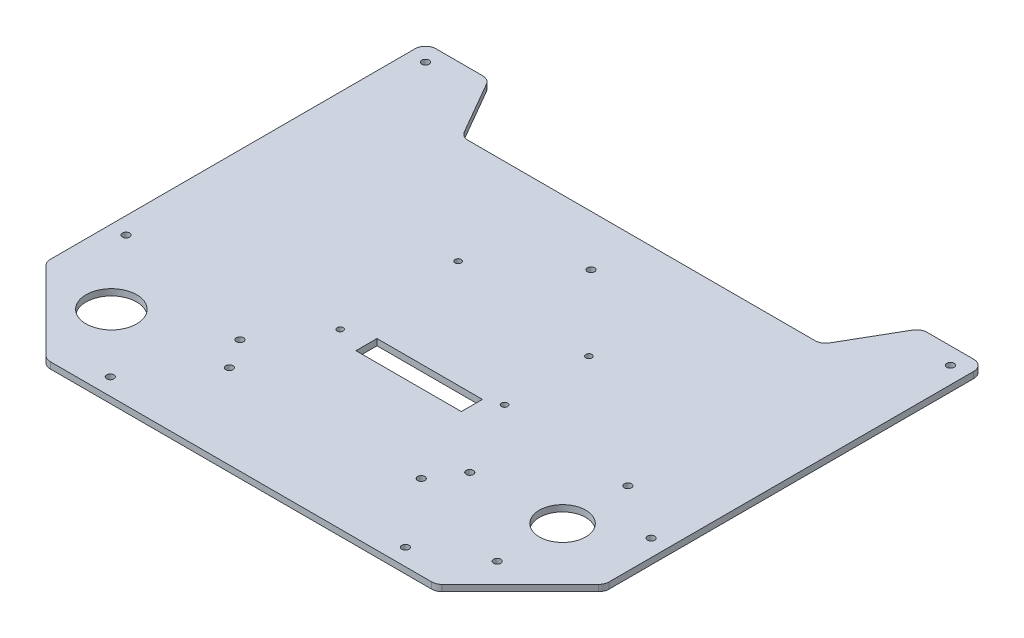
SolidWorks part; units mm, degrees
material "Acier non allié"
ref_plane "Front" through (0, 0, 0) normal (0, 0, 1) x (1, 0, 0)
ref_plane "Top" through (0, 0, 0) normal (0, 1, 0) x (1, 0, 0)
ref_plane "Right" through (0, 0, 0) normal (1, 0, 0) x (0, 0, -1)
sketch "Esquisse1" plane through (0, 0, 0) normal (0, 1, 0) x (1, 0, 0)
  line L0 (0, 0) -> (0, 1919.0564) construction
  line L1 (-92.5, 0) -> (92.5, 0)
  line L2 (92.5, 0) -> (132.5, 40)
  line L3 (132.5, 40) -> (132.5, 220)
  line L4 (132.5, 220) -> (102.5, 220)
  line L5 (102.5, 220) -> (85.1795, 190)
  line L6 (85.1795, 190) -> (-85.1795, 190)
  line L7 (-102.5, 220) -> (-85.1795, 190)
  line L8 (-132.5, 220) -> (-102.5, 220)
  line L9 (-132.5, 40) -> (-132.5, 220)
  line L10 (-92.5, 0) -> (-132.5, 40)
  point P12 (0, 190)
  dimension "D1" = 132.5
  dimension "D2" = 220
  dimension "D3" = 30
  dimension "D4" = 30
  dimension "D5" = 40
  dimension "D6" = 40
  dimension "D7" = 60
extrude "Boss.-Extru.1" add sketch "Esquisse1" along normal blind 3
fillet "Congé1" radius 5 10 edges at (132.5, 1.5, -220) (102.5, 1.5, -220) (85.1795, 1.5, -190) (-85.1795, 1.5, -190) (-102.5, 1.5, -220) (-132.5, 1.5, -220) (-132.5, 1.5, -40) (-92.5, 1.5, 0) (92.5, 1.5, 0) (132.5, 1.5, -40)
sketch "Esquisse2" plane through (0, 0, 0) normal (0, -1, 0) x (1, 0, 0)
  line L0 (0, 0) -> (0, -330.9968) construction
  line L1 (-90.4289, 0) -> (90.4289, 0) construction
  line L2 (-105.3868, -220) -> (-127.5, -220) construction
  line L3 (-132.5, -215) -> (-132.5, -42.0711) construction
  circle A0 centre (-70, -8) radius 1
  circle A1 centre (-124.5, -70) radius 1
  circle A2 centre (-124.5, -212) radius 1
  circle A3 centre (124.5, -212) radius 1
  circle A4 centre (124.5, -70) radius 1
  circle A5 centre (70, -8) radius 1
  dimension "D3" = 2
  dimension "D6" = 2
  dimension "D9" = 2
  dimension "D1" = 70
  dimension "D2" = 8
  dimension "D4" = 124.5
  dimension "D5" = 70
  dimension "D7" = 8
  dimension "D8" = 8
extrude "Enlèv. mat.-Extru.1" cut sketch "Esquisse2" against normal through all
hole_wizard "Dégagement M31" positions "Esquisse3" profile "Esquisse4" hole size "M3" standard "ISO" end condition through all
sketch "Esquisse3" plane through (0, 0, 0) normal (0, -1, 0) x (-1, 0, 0)
  point P0 (-70, 8)
  point P3 (-124.5, 70)
  point P6 (-124.5, 212)
  point P9 (124.5, 212)
  point P12 (124.5, 70)
  point P15 (70, 8)
sketch "Esquisse4" plane through (70, 0, -8) normal (1, 0, 0) x (0, 0, -1)
  line L0 (0, 0) -> (0, 3)
  line L1 (0, 3) -> (1.7, 3)
  line L2 (1.7, 3) -> (1.7, 0)
  line L5 (1.7, 0) -> (0, 0)
  line L11 (0, -6.35) -> (0, 107.95) construction
  dimension "Diamètre du perçage jusqu'au prochain" = 3.4
  dimension "Profondeur du perçage jusqu'au prochain" = 3
sketch "Esquisse5" plane through (0, 0, 0) normal (0, -1, 0) x (1, 0, 0)
  line L0 (-35, -138) -> (-35, -82) construction
  line L5 (35, -130) -> (35, -90) construction
  line L6 (132.5, -42.0711) -> (132.5, -215) construction
  line L7 (97.5, -86) -> (97.5, -24) construction
  line L20 (-132.5, -215) -> (-132.5, -42.0711) construction
  line L21 (-90.4289, 0) -> (90.4289, 0) construction
  line L22 (-105.3868, -220) -> (-127.5, -220) construction
  line L27 (-45.5, -40) -> (45.5, -40) construction
  line L28 (127.5, -220) -> (105.3868, -220) construction
  line L29 (-54.5, -54) -> (54.5, -54) construction
  line L30 (-54.5, -54) -> (-54.5, -166) construction
  line L31 (-54.5, -166) -> (54.5, -166) construction
  line L32 (54.5, -54) -> (54.5, -166) construction
  line L34 (-22.5, -87) -> (27.5, -87)
  line L35 (-22.5, -87) -> (-22.5, -77)
  line L36 (-22.5, -77) -> (27.5, -77)
  line L37 (27.5, -87) -> (27.5, -77)
  circle A0 centre (-97.5, -36) radius 12
  circle A1 centre (-45.5, -40) radius 1.5
  circle A2 centre (45.5, -40) radius 1.5
  circle A3 centre (97.5, -55) radius 11
  circle A4 centre (97.5, -86) radius 1.5
  circle A5 centre (97.5, -24) radius 1.5
  circle A6 centre (-35, -138) radius 1
  circle A7 centre (-35, -82) radius 1
  circle A8 centre (35, -130) radius 1
  circle A9 centre (35, -90) radius 1
  circle A10 centre (0, -166) radius 1.5
  circle A11 centre (-54.5, -54) radius 1.5
  circle A12 centre (54.5, -54) radius 1.5
  point P8 (97.5, -55)
  point P18 (-35, -110)
  point P23 (0, -166)
  point P29 (54.5, -110)
  point P47 (-22.5, -82)
  point P48 (2.5, -77)
  dimension "D10" = 24
  dimension "D15" = 3
  dimension "D16" = 3
  dimension "D2" = 22
  dimension "D6" = 3
  dimension "D7" = 3
  dimension "D20" = 2
  dimension "D21" = 2
  dimension "D27" = 2
  dimension "D28" = 2
  dimension "D14" = 3
  dimension "D30" = 3
  dimension "D31" = 3
  dimension "D8" = 35
  dimension "D9" = 36
  dimension "D17" = 91
  dimension "D18" = 40
  dimension "D19" = 87
  dimension "D3" = 35
  dimension "D4" = 55
  dimension "D5" = 62
  dimension "D22" = 110
  dimension "D23" = 97.5
  dimension "D24" = 56
  dimension "D25" = 8
  dimension "D26" = 40
  dimension "D29" = 70
  dimension "D11" = 109
  dimension "D12" = 112
  dimension "D13" = 110
  dimension "D32" = 50
  dimension "D33" = 10
  dimension "D34" = 135
extrude "Enlèv. mat.-Extru.2" cut sketch "Esquisse5" against normal through all
fillet "Congé2" [suppressed] radius 3
hole_wizard "Dégagement M32" positions "Esquisse6" profile "Esquisse7" hole size "M3" standard "ISO" end condition up to next
sketch "Esquisse6" plane through (0, 3, 0) normal (0, 1, 0) x (1, 0, 0)
  point P0 (-45.5, 40)
  point P3 (45.5, 40)
  point P7 (97.5, 86)
  point P10 (97.5, 24)
  point P13 (-54.5, 54)
  point P16 (54.5, 54)
  point P19 (0, 166)
sketch "Esquisse7" plane through (-45.5, 3, -40) normal (1, 0, 0) x (0, 0, 1)
  line L0 (0, 0) -> (0, 3)
  line L1 (0, 3) -> (1.7, 3)
  line L2 (1.7, 3) -> (1.7, 0)
  line L5 (1.7, 0) -> (0, 0)
  line L11 (0, -6.35) -> (0, 107.95) construction
  dimension "Diamètre du perçage jusqu'au prochain" = 3.4
  dimension "Profondeur du perçage jusqu'au prochain" = 3
hole_wizard "Dégagement M2.51" positions "Esquisse8" profile "Esquisse9" hole size "M2.5" standard "ISO" end condition up to next
sketch "Esquisse8" plane through (0, 3, 0) normal (0, 1, 0) x (1, 0, 0)
  point P0 (-35, 138)
  point P3 (-35, 82)
  point P6 (35, 90)
  point P9 (35, 130)
sketch "Esquisse9" plane through (-35, 3, -138) normal (1, 0, 0) x (0, 0, 1)
  line L0 (0, 0) -> (0, 3)
  line L1 (0, 3) -> (1.45, 3)
  line L2 (1.45, 3) -> (1.45, 0)
  line L5 (1.45, 0) -> (0, 0)
  line L11 (0, -6.35) -> (0, 107.95) construction
  dimension "Diamètre du perçage jusqu'au prochain" = 2.9
  dimension "Profondeur du perçage jusqu'au prochain" = 3
equation "\"WIDTH\"= 300mm'Total width of the robot"
equation "\"LENGTH\"= 220mm'Total length of the robot"
equation "\"CUT_DEPTH\"= 45mm'Depth of the cut on the edges of the plate"
equation "\"Plate_th\"= 3mm'Thickness of the plate"
equation "\"D1\"= \"Plate_th\""
equation "\"D23@Esquisse5\"=(265-70)/2"
